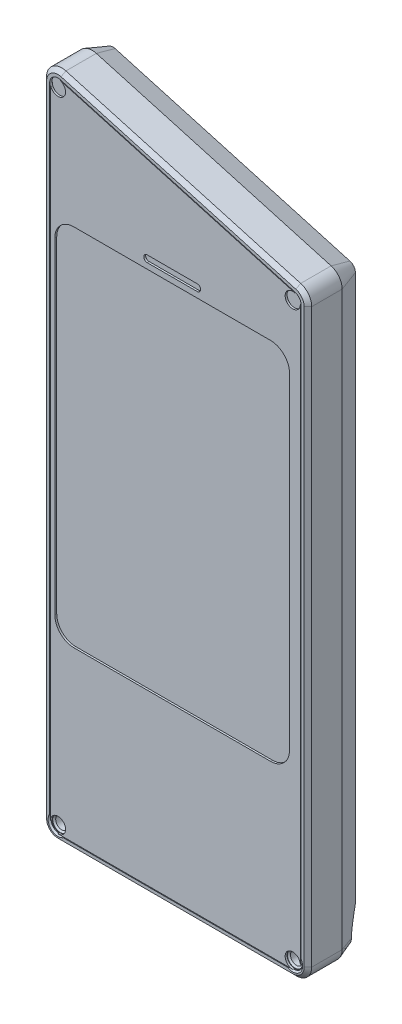
SolidWorks part; units mm, degrees
ref_plane "Front Plane" through (0, 0, 0) normal (0, 0, 1) x (1, 0, 0)
ref_plane "Top Plane" through (0, 0, 0) normal (0, 1, 0) x (1, 0, 0)
ref_plane "Right Plane" through (0, 0, 0) normal (1, 0, 0) x (0, 0, -1)
sketch "Sketch1" plane through (0, 0, 0) normal (0, 0, 1) x (1, 0, 0)
  line L0 (17.8556, 135.8892) -> (77.5009, 118.9644) construction
  line L1 (-31.968, 151.0665) -> (37.832, 131.2602)
  line L2 (-31.968, 151.0665) -> (-31.968, -26.3403)
  line L3 (-31.968, -26.3403) -> (37.832, -26.3403)
  line L4 (37.832, 131.2602) -> (37.832, -26.3403)
  arc A0 (-27.968, -23.9403) -> (-29.5672, -22.3911) centre (-27.968, -22.3403) ccw construction
  circle A1 centre (-27.968, -22.3403) radius 1.6
  arc A2 (35.4312, -22.3911) -> (33.832, -23.9403) centre (33.832, -22.3403) ccw construction
  circle A3 centre (33.832, -22.3403) radius 1.6
  dimension "D1" = 4
  dimension "D2" = 4
  dimension "D3" = 4
  dimension "D4" = 1
extrude "Boss-Extrude1" add sketch "Sketch1" against normal blind 14.5 from offset 0.5
fillet "Fillet1" radius 4 4 edges at (37.832, 131.2602, -6.75) (37.832, -26.3403, -6.75) (-31.968, -26.3403, -6.75) (-31.968, 151.0665, -6.75)
chamfer "Chamfer1" distance 2 angle 70 10 edges at (-30.3797, 148.9648, -14) (-31.968, 61.7167, -14) (-30.7965, -25.1687, -14) (2.932, -26.3403, -14) (36.6604, -25.1687, -14) (37.832, 52.9485, -14) (37.0232, 130.649, -14) (4.0239, 140.8535, -14) (-26.368, -22.3403, -14) (35.432, -22.3403, -14) first distance on face at (35.432, -22.3403, -14) first distance on face at (-26.368, -22.3403, -14)
chamfer "Chamfer2" distance 1 angle 45 10 edges at (36.6604, -25.1687, 0.5) (2.932, -26.3403, 0.5) (-30.7965, -25.1687, 0.5) (-31.968, 61.7167, 0.5) (-30.3797, 148.9648, 0.5) (4.0239, 140.8535, 0.5) (37.0232, 130.649, 0.5) (37.832, 52.9485, 0.5) (-26.368, -22.3403, 0.5) (35.432, -22.3403, 0.5)
sketch "Sketch2" plane through (0, 0, 0.5) normal (0, 0, 1) x (1, 0, 0)
  line L4 (-4.5014, 118.5003) -> (8.6929, 118.5003) construction
  line L5 (-23.7966, 116.1206) -> (27.9881, 116.1206)
  line L6 (-28.7966, 111.1206) -> (-28.7966, 25.1678)
  line L7 (-23.7966, 20.1678) -> (27.9881, 20.1678)
  line L8 (-27.968, -24.3403) -> (33.832, -24.3403)
  line L9 (35.832, -22.3403) -> (35.832, 128.2374)
  line L10 (34.3779, 130.1614) -> (-27.4221, 147.6976)
  line L11 (-29.968, 145.7736) -> (-29.968, -22.3403)
  line L12 (-27.968, -24.3403) -> (33.832, -24.3403)
  line L13 (35.832, -22.3403) -> (35.832, 128.2374)
  line L14 (34.3779, 130.1614) -> (-27.4221, 147.6976)
  line L15 (-29.968, 145.7736) -> (-29.968, -22.3403)
  line L16 (32.9881, 111.1206) -> (32.9881, 25.1678)
  line L17 (2.0958, 20.1678) -> (2.0958, 116.1206) construction
  line L18 (-28.7966, 68.1442) -> (32.9881, 68.1442) construction
  line L19 (-4.5014, 119.3827) -> (8.6929, 119.3827)
  line L20 (-4.5014, 117.6178) -> (8.6929, 117.6178)
  arc A5 (-23.7966, 20.1678) -> (-28.7966, 25.1678) centre (-23.7966, 25.1678) cw
  arc A6 (32.9881, 25.1678) -> (27.9881, 20.1678) centre (27.9881, 25.1678) cw
  arc A7 (27.9881, 116.1206) -> (32.9881, 111.1206) centre (27.9881, 111.1206) cw
  arc A8 (-23.7966, 116.1206) -> (-28.7966, 111.1206) centre (-23.7966, 111.1206) ccw
  arc A9 (33.832, -24.3403) -> (35.832, -22.3403) centre (33.832, -22.3403) ccw
  arc A10 (35.832, 128.2374) -> (34.3779, 130.1614) centre (33.832, 128.2374) ccw
  arc A11 (-27.4221, 147.6976) -> (-29.968, 145.7736) centre (-27.968, 145.7736) ccw
  arc A12 (-29.968, -22.3403) -> (-27.968, -24.3403) centre (-27.968, -22.3403) ccw
  arc A17 (-4.5014, 119.3827) -> (-4.5014, 117.6178) centre (-4.5014, 118.5003) ccw
  arc A18 (8.6929, 117.6178) -> (8.6929, 119.3827) centre (8.6929, 118.5003) ccw
  arc A19 (-29.968, 145.7736) -> (-27.4221, 147.6976) centre (-27.968, 145.7736) ccw
  arc A20 (34.3779, 130.1614) -> (35.832, 128.2374) centre (33.832, 128.2374) ccw
  arc A21 (-29.968, -22.3403) -> (-27.968, -24.3403) centre (-27.968, -22.3403) cw
  arc A22 (33.832, -24.3403) -> (35.832, -22.3403) centre (33.832, -22.3403) cw
  point P0 (2.0958, 68.1442)
  point P17 (2.0958, 118.5003)
  dimension "D2" = 5
  dimension "D1" = 1
extrude "Boss-Extrude2" add sketch "Sketch2" along normal blind 0.5 from offset 0.5 separate body offset against normal yes
sketch "Sketch3" plane through (0, 0, 0.5) normal (0, 0, 1) x (1, 0, 0)
  line L8 (-27.968, -24.5403) -> (33.832, -24.5403)
  line L9 (36.032, -22.3403) -> (36.032, 128.2374)
  line L10 (34.4325, 130.3538) -> (-27.3675, 147.89)
  line L11 (-30.168, 145.7736) -> (-30.168, -22.3403)
  line L12 (-27.968, -24.5403) -> (33.832, -24.5403)
  line L13 (36.032, -22.3403) -> (36.032, 128.2374)
  line L14 (34.4325, 130.3538) -> (-27.3675, 147.89)
  line L15 (-30.168, 145.7736) -> (-30.168, -22.3403)
  arc A8 (33.832, -24.5403) -> (36.032, -22.3403) centre (33.832, -22.3403) ccw
  arc A9 (36.032, 128.2374) -> (34.4325, 130.3538) centre (33.832, 128.2374) ccw
  arc A10 (-27.3675, 147.89) -> (-30.168, 145.7736) centre (-27.968, 145.7736) ccw
  arc A11 (-30.168, -22.3403) -> (-27.968, -24.5403) centre (-27.968, -22.3403) ccw
  arc A12 (33.832, -24.5403) -> (36.032, -22.3403) centre (33.832, -22.3403) ccw
  arc A13 (36.032, 128.2374) -> (34.4325, 130.3538) centre (33.832, 128.2374) ccw
  arc A14 (-27.3675, 147.89) -> (-30.168, 145.7736) centre (-27.968, 145.7736) ccw
  arc A15 (-30.168, -22.3403) -> (-27.968, -24.5403) centre (-27.968, -22.3403) ccw
  dimension "D1" = 0.8
extrude "Cut-Extrude2" cut sketch "Sketch3" against normal blind 0.6
